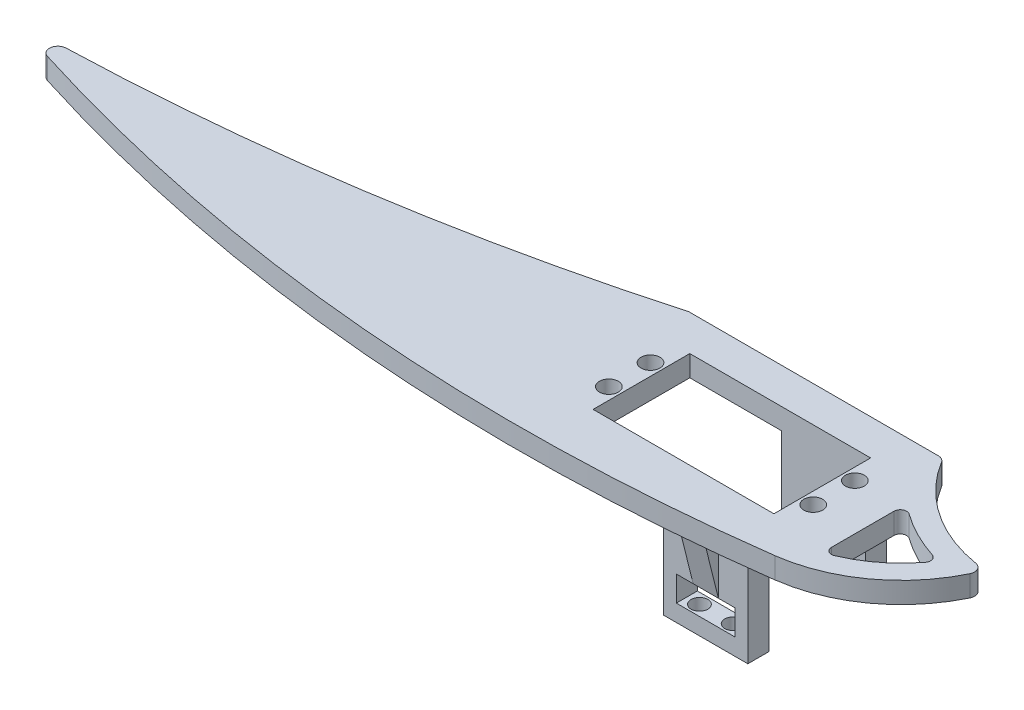
SolidWorks part; units mm, degrees
ref_plane "Front Plane" through (0, 0, 0) normal (0, 0, 1) x (1, 0, 0)
ref_plane "Top Plane" through (0, 0, 0) normal (0, 1, 0) x (1, 0, 0)
ref_plane "Right Plane" through (0, 0, 0) normal (1, 0, 0) x (0, 0, -1)
sketch "Sketch1" plane through (0, 0, 0) normal (0, 1, 0) x (1, 0, 0)
  line L1 (-30.25, 20) -> (30.25, 20)
  line L2 (-30.25, 20) -> (-30.25, -20)
  line L3 (-30.25, -20) -> (30.25, -20)
  line L4 (30.25, 20) -> (30.25, -20)
  line L5 (-30.25, 20) -> (30.25, -20) construction
  line L6 (-30.25, -20) -> (30.25, 20) construction
  line L7 (-21.5, 11.5) -> (21.5, 11.5)
  line L8 (-21.5, 11.5) -> (-21.5, -11.5)
  line L9 (-21.5, -11.5) -> (21.5, -11.5)
  line L10 (21.5, 11.5) -> (21.5, -11.5)
  line L11 (-21.5, 11.5) -> (21.5, -11.5) construction
  line L12 (-21.5, -11.5) -> (21.5, 11.5) construction
  point P0 (0, 0)
  point P6 (0, 0)
  dimension "D1" = 60.5
  dimension "D2" = 40
  dimension "D3" = 43
  dimension "D4" = 23
extrude "Boss-Extrude1" add sketch "Sketch1" along normal mid plane 5
sketch "Sketch2" plane through (0, 2.5, 0) normal (0, 1, 0) x (1, 0, 0)
  line L0 (30.25, 20) -> (30.25, -20)
  line L1 (30.25, 20) -> (-30.25, 20) construction
  line L2 (35.25, 6.3668) -> (35.25, -13.7227)
  arc A0 (30.25, 20) -> (58.25, 2) centre (61.5119, 37.8519) ccw
  arc A2 (30.25, -20) -> (58.25, 2) centre (25.6332, 14.6942) ccw
  arc A3 (35.25, 6.3668) -> (50.7506, -1.7106) centre (61.5119, 37.8519) ccw
  arc A4 (35.25, -13.7227) -> (50.7506, -1.7106) centre (25.6332, 14.6942) ccw
  dimension "D3" = 36
  dimension "D4" = 35
  dimension "D1" = 18
  dimension "D2" = 28
  dimension "D5" = 5
extrude "Boss-Extrude2" add sketch "Sketch2" against normal up to surface (5 mm away) up to face at (0, -2.5, 0)
sketch "Sketch3" plane through (0, 2.5, 0) normal (0, 1, 0) x (1, 0, 0)
  line L0 (-30.25, 0) -> (-170.25, 0) construction
  line L1 (-30.25, 20) -> (-30.25, -20) construction
  line L2 (-30.25, 20) -> (-30.25, -20)
  line L3 (-30.25, -20) -> (30.25, -20)
  arc A2 (-30.25, 20) -> (-170.25, 0) centre (-175.96, 539.9698) cw
  arc A3 (30.25, -20) -> (-170.25, 0) centre (-27.6191, 414.8687) cw
  arc A4 (30.25, -20) -> (58.25, 2) centre (25.6332, 14.6942) ccw construction
  dimension "D2" = 540
  dimension "D1" = 140
extrude "Boss-Extrude3" add sketch "Sketch3" against normal up to surface (5 mm away) up to face at (11.8103, -2.5, 1.0515)
sketch "Sketch4" plane through (0, 2.5, 0) normal (0, 1, 0) x (1, 0, 0)
  line L0 (-24.3, 4.95) -> (-24.3, -4.95) construction
  line L1 (0, 0) -> (0, -11.5) construction
  line L2 (-21.5, -11.5) -> (21.5, -11.5) construction
  circle A0 centre (-24.3, 4.95) radius 2.25
  circle A1 centre (-24.3, -4.95) radius 2.25
  circle A4 centre (24.3, -4.95) radius 2.25
  circle A5 centre (24.3, 4.95) radius 2.25
  point P8 (-24.3, 0)
  dimension "D1" = 4.5
  dimension "D3" = 9.9
  dimension "D2" = 24.3
extrude "Cut-Extrude1" cut sketch "Sketch4" against normal through all
sketch "Sketch6" plane through (0, 2.5, 0) normal (0, 1, 0) x (1, 0, 0)
  line L0 (0, 0) -> (21.5, 0) construction
  line L1 (0.3, 16.5) -> (20.3, 16.5)
  line L2 (0.3, 16.5) -> (0.3, 11.5)
  line L3 (0.3, 11.5) -> (20.3, 11.5)
  line L4 (20.3, 16.5) -> (20.3, 11.5)
  line L5 (21.5, -11.5) -> (21.5, 11.5) construction
  line L6 (0.3, -11.5) -> (20.3, -11.5)
  line L7 (20.3, -16.5) -> (20.3, -11.5)
  line L8 (0.3, -16.5) -> (20.3, -16.5)
  line L9 (0.3, -16.5) -> (0.3, -11.5)
  line L10 (21.5, 11.5) -> (-21.5, 11.5) construction
  circle A0 centre (24.3, 4.95) radius 2.25 construction
  point P15 (10.3, 16.5)
  dimension "D1" = 20
  dimension "D2" = 5
  dimension "D3" = 14
extrude "Boss-Extrude4" add sketch "Sketch6" against normal blind 24 from surface starting at face at (24.3, -2.5, -7.2)
sketch "Sketch7" plane through (0, 0, 16.5) normal (0, 0, 1) x (1, 0, 0)
  line L0 (0.3, -26.5) -> (20.3, -26.5) construction
  line L1 (3.3, -16.5) -> (17.3, -16.5)
  line L2 (3.3, -16.5) -> (3.3, -22.5)
  line L3 (3.3, -22.5) -> (17.3, -22.5)
  line L4 (17.3, -16.5) -> (17.3, -22.5)
  line L5 (0.3, -26.5) -> (20.3, -26.5) construction
  point P6 (10.3, -26.5)
  point P7 (10.3, -16.5)
  dimension "D1" = 14
  dimension "D2" = 6
  dimension "D3" = 4
extrude "Cut-Extrude3" cut sketch "Sketch7" against normal through all
ref_plane "Plane1" through (10.3, 0, 0) normal (1, 0, 0) x (0, 0, -1)
fillet "Fillet1" radius 2 1 edges at (-170.25, 0, 0)
fillet "Fillet2" radius 2 2 edges at (58.25, 0, -2) (30.25, 0, -20)
fillet "Fillet3" radius 1.5 3 edges at (50.7506, 0, 1.7106) (35.25, 0, 13.7227) (35.25, 0, -6.3668)
sketch "Sketch8" plane through (0, -26.5, 0) normal (0, -1, 0) x (1, 0, 0)
  line L0 (0.3, 11.5) -> (0.3, 16.5) construction
  line L1 (6.3, 14) -> (14.3, 14) construction
  line L2 (0.3, 16.5) -> (20.3, 16.5) construction
  circle A0 centre (6.3, 14) radius 2
  circle A1 centre (14.3, 14) radius 2
  point P4 (10.3, 14)
  point P8 (0.3, 14)
  point P10 (10.3, 16.5)
  dimension "D1" = 4
  dimension "D2" = 8
extrude "Cut-Extrude4" cut sketch "Sketch8" against normal up to next
sketch "Sketch9" plane through (10.3, 0, 0) normal (1, 0, 0) x (0, 0, -1)
  line L0 (-20, -2.5) -> (-16.5, -16.5)
  line L1 (-23.8335, -2.5) -> (-3.6579, -2.5) construction
  line L2 (-16.5, -26.5) -> (-16.5, -2.5) construction
  line L3 (-16.5, -16.5) -> (-16.5, -2.5)
  line L4 (-16.5, -2.5) -> (-20, -2.5)
  dimension "D1" = 14
  dimension "D2" = 3.5
extrude "Boss-Extrude5" add sketch "Sketch9" along normal mid plane 6
mirror "Mirror1" about plane through (0, 0, 0) normal (0, 0, 1) of "Boss-Extrude5", "Cut-Extrude4"
fillet "Fillet4" radius 2 9 edges at (3.8, -2.5, 16.5) (7.3, -2.5, 18.25) (10.3, -2.5, 20) (13.3, -2.5, 18.25) (16.8, -2.5, 16.5) (16.8, -2.5, -16.5) (3.8, -2.5, -16.5) (7.3, -2.5, -18.25) (13.3, -2.5, -18.25)
